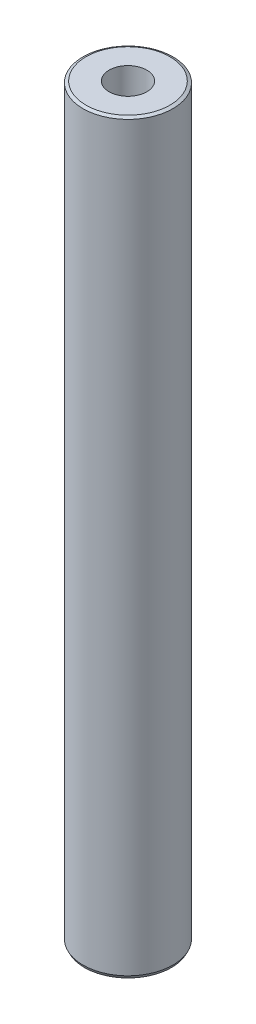
SolidWorks part; units mm, degrees
ref_plane "Front Plane" through (0, 0, 0) normal (0, 0, 1) x (1, 0, 0)
ref_plane "Top Plane" through (0, 0, 0) normal (0, 1, 0) x (1, 0, 0)
ref_plane "Right Plane" through (0, 0, 0) normal (1, 0, 0) x (0, 0, -1)
sketch "Sketch1" plane through (0, 0, 0) normal (0, 1, 0) x (1, 0, 0)
  circle A0 centre (0, 0) radius 22.5
  dimension "SHAFT_OD" = 45
extrude "Boss-Extrude1" add sketch "Sketch1" along normal blind 373.4548
sketch "Sketch2" plane through (0, 0, 0) normal (0, 1, 0) x (1, 0, 0)
  circle A0 centre (0, 0) radius 9.4317
  dimension "BORE_D" = 18.8634
extrude "Cut-Extrude1" cut sketch "Sketch2" along normal through all
chamfer "Chamfer1" distance 0.7621 angle 62.93 2 edges at (0, 373.4548, 22.5) (0, 0, 22.5) first distance on face at (0, 373.4548, 22.5) first distance on face at (0, 0, 9.4317)
